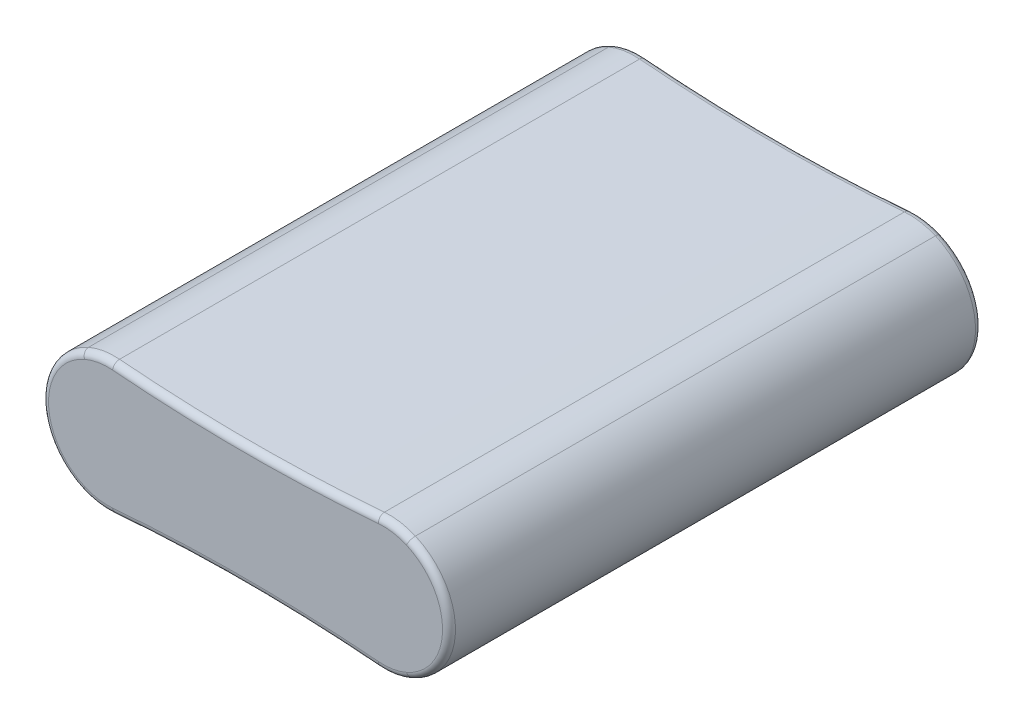
SolidWorks part; units mm, degrees
material "1060 Alloy"
ref_plane "Front Plane" through (0, 0, 0) normal (0, 0, 1) x (1, 0, 0)
ref_plane "Top Plane" through (0, 0, 0) normal (0, 1, 0) x (1, 0, 0)
ref_plane "Right Plane" through (0, 0, 0) normal (1, 0, 0) x (0, 0, -1)
sketch "Sketch1" plane through (0, 0, 0) normal (0, 0, 1) x (1, 0, 0)
  line L0 (-40.005, 0) -> (40.005, 0) construction
  line L1 (-26.924, 0) -> (26.924, 0) construction
  line L2 (-26.924, 13.081) -> (26.924, 13.081) construction
  line L3 (-26.924, -13.081) -> (26.924, -13.081) construction
  line L4 (0, 11.938) -> (0, -11.938) construction
  arc A0 (-26.924, 13.081) -> (-26.924, -13.081) centre (-26.924, 0) ccw construction
  arc A1 (26.924, -13.081) -> (26.924, 13.081) centre (26.924, 0) ccw construction
  arc A2 (-26.924, -13.081) -> (26.924, -13.081) centre (0, -329.6144) cw
  arc A3 (-26.924, 13.081) -> (26.924, 13.081) centre (0, 329.6144) ccw
  arc A4 (-26.924, 13.081) -> (-26.924, -13.081) centre (-26.924, 0) ccw
  arc A5 (26.924, -13.081) -> (26.924, 13.081) centre (26.924, 0) ccw
  point P5 (0, 0)
  dimension "D3" = 23.876
  dimension "D1" = 80.01
  dimension "D2" = 26.162
extrude "Boss-Extrude1" add sketch "Sketch1" along normal mid plane 104.775
fillet "Fillet1" radius 12.7 4 edges at (26.924, -13.081, 0) (-26.924, -13.081, 0) (-26.924, 13.081, 0) (26.924, 13.081, 0)
fillet "Fillet2" radius 1.27 16 edges at (29.1512, 12.8787, -52.3875) (40.005, 0, -52.3875) (29.1512, -12.8787, -52.3875) (0, -11.938, -52.3875) (-29.1512, -12.8787, -52.3875) (-40.005, 0, -52.3875) (-29.1512, 12.8787, -52.3875) (29.1512, 12.8787, 52.3875) (40.005, 0, 52.3875) (29.1512, -12.8787, 52.3875) (0, -11.938, 52.3875) (-29.1512, -12.8787, 52.3875) (-40.005, 0, 52.3875) (-29.1512, 12.8787, 52.3875) (0, 11.938, -52.3875) (0, 11.938, 52.3875)
